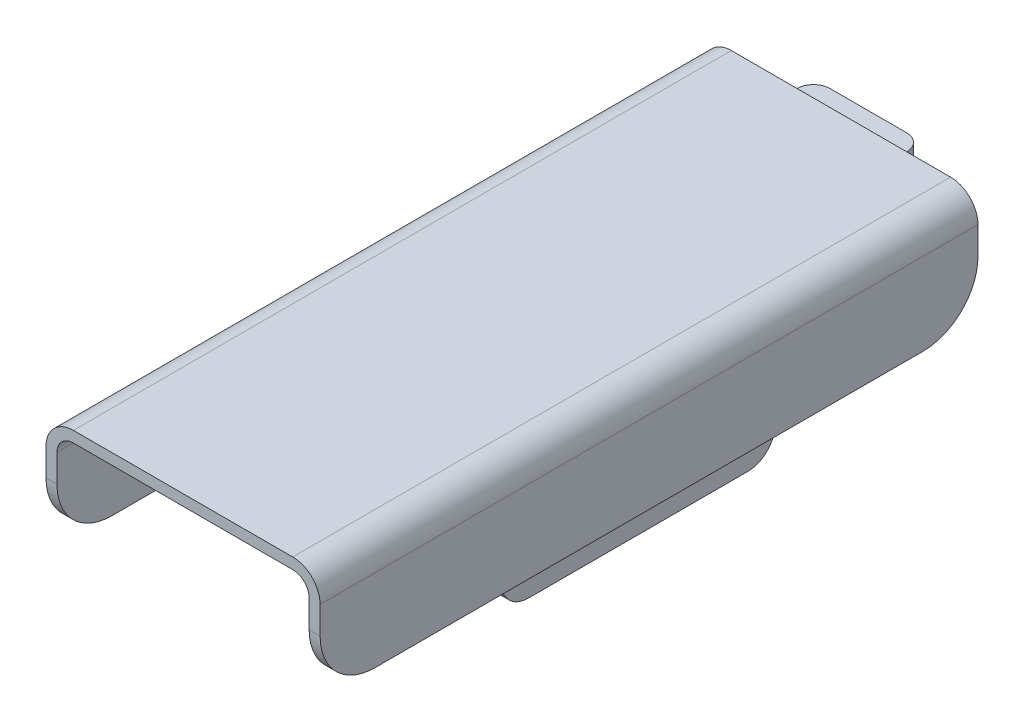
SolidWorks part; units mm, degrees
ref_plane "Front Plane" through (0, 0, 0) normal (0, 0, 1) x (1, 0, 0)
ref_plane "Top Plane" through (0, 0, 0) normal (0, 1, 0) x (1, 0, 0)
ref_plane "Right Plane" through (0, 0, 0) normal (1, 0, 0) x (0, 0, -1)
sketch "Sketch1" plane through (0, 0, 0) normal (0, 0, 1) x (1, 0, 0)
  line L0 (-62.3906, 20.6479) -> (-62.3906, 26.5485) construction
  line L1 (-62.3906, 20.6479) -> (-62.3906, -14.3521) construction
  line L2 (-14.3906, 5.6479) -> (-14.3906, 20.6479)
  line L4 (-17.3906, 23.6479) -> (-57.3906, 23.6479)
  line L5 (-60.3906, 20.6479) -> (-60.3906, 5.6479)
  line L6 (-60.3906, 5.6479) -> (-62.3906, 5.6479)
  line L7 (-14.3906, 5.6479) -> (-12.3906, 5.6479)
  line L16 (-17.3906, 25.6479) -> (-57.3906, 25.6479)
  line L17 (-62.3906, 20.6479) -> (-62.3906, 5.6479)
  line L23 (-12.3906, 5.6479) -> (-12.3906, 20.6479)
  arc A0 (-57.3906, 25.6479) -> (-62.3906, 20.6479) centre (-57.3906, 20.6479) ccw
  arc A1 (-17.3906, 25.6479) -> (-12.3906, 20.6479) centre (-17.3906, 20.6479) cw
  arc A2 (-17.3906, 23.6479) -> (-14.3906, 20.6479) centre (-17.3906, 20.6479) cw
  arc A3 (-57.3906, 23.6479) -> (-60.3906, 20.6479) centre (-57.3906, 20.6479) ccw
  dimension "D4" = 20
  dimension "D1" = 5
  dimension "D2" = 2
  dimension "D3" = 20
extrude "Boss-Extrude1" add sketch "Sketch1" along normal blind 120
fillet "Fillet1" radius 10 4 edges at (-13.3906, 5.6479, 120) (-13.3906, 5.6479, 0) (-61.3906, 5.6479, 0) (-61.3906, 5.6479, 120)
sketch "Sketch2" plane through (0, 5.6479, 0) normal (0, -1, 0) x (1, 0, 0)
  line L0 (-60.3906, 85) -> (-12.3906, 85) construction
  line L1 (-57.3906, 35) -> (-60.3906, 35)
  line L2 (-57.3906, 35) -> (-57.3906, 85)
  line L3 (-57.3906, 85) -> (-60.3906, 85)
  line L4 (-60.3906, 35) -> (-60.3906, 85)
  line L5 (-12.3906, 135.2288) -> (-12.3906, -153) construction
  line L9 (-12.3906, 35) -> (-12.3906, 85) construction
  line L10 (-15.3906, 85) -> (-12.3906, 85) construction
  line L11 (-15.3906, 35) -> (-15.3906, 85) construction
  line L12 (-15.3906, 35) -> (-12.3906, 35) construction
  point P18 (0, 0)
extrude "Boss-Extrude2" add sketch "Sketch2" against normal up to surface and the other way blind 5 up to face at (-59.2012, 22.4586, 60)
sketch "Sketch12" plane through (0, 5.6479, 0) normal (0, -1, 0) x (1, 0, 0)
  line L0 (-37.3906, 120) -> (-37.3906, 0) construction
  line L1 (-57.3906, 120) -> (-17.3906, 120) construction
  line L2 (-57.3906, 0) -> (-17.3906, 0) construction
  line L3 (-14.3906, 35) -> (-17.3906, 35)
  line L4 (-57.3906, 35) -> (-57.3906, 85)
  line L5 (-57.3906, 85) -> (-60.3906, 85)
  line L6 (-60.3906, 85) -> (-60.3906, 35)
  line L7 (-60.3906, 35) -> (-57.3906, 35)
  line L8 (-57.3906, 35) -> (-57.3906, 85) construction
  line L9 (-57.3906, 85) -> (-60.3906, 85) construction
  line L10 (-60.3906, 85) -> (-60.3906, 35) construction
  line L11 (-60.3906, 35) -> (-57.3906, 35) construction
  line L12 (-14.3906, 85) -> (-14.3906, 35)
  line L13 (-17.3906, 85) -> (-14.3906, 85)
  line L14 (-17.3906, 35) -> (-17.3906, 85)
  dimension "D1" = 0
extrude "Boss-Extrude5" add sketch "Sketch12" against normal up to surface and the other way blind 5 up to face at (-15.5799, 22.4586, 60)
sketch "Sketch3" plane through (0, 23.6479, 0) normal (0, -1, 0) x (1, 0, 0)
  line L0 (-37.3906, 0) -> (-37.3906, 120) construction
  line L1 (-27.3906, 10) -> (-47.3906, 10)
  line L2 (-27.3906, 10) -> (-27.3906, -5)
  line L3 (-27.3906, -5) -> (-47.3906, -5)
  line L4 (-47.3906, 10) -> (-47.3906, -5)
  line L6 (-12.3906, 0) -> (-12.3906, 10) construction
  point P8 (0, 0)
  point P9 (0, 0)
  point P10 (-37.3906, 120)
  dimension "D1" = 10
  dimension "D2" = 20
  dimension "D3" = 15
  dimension "D4" = 25
extrude "Boss-Extrude3" add sketch "Sketch3" along normal blind 3
fillet "Fillet2" radius 5 4 edges at (-58.8906, 0.6479, 35) (-58.8906, 0.6479, 85) (-15.8906, 0.6479, 85) (-15.8906, 0.6479, 35)
chamfer "Chamfer1" distance 4 angle 45 1 edges at (-37.3906, 23.6479, 10)
fillet "Fillet3" radius 4 2 edges at (-37.3906, 20.6479, 11) (-37.3906, 23.6479, 14)
fillet "Fillet4" radius 3 2 edges at (-47.3906, 22.1479, -5) (-27.3906, 22.1479, -5)
fillet "Fillet5" radius 3 2 edges at (-17.3906, 23.6479, 60) (-57.3906, 23.6479, 60)
